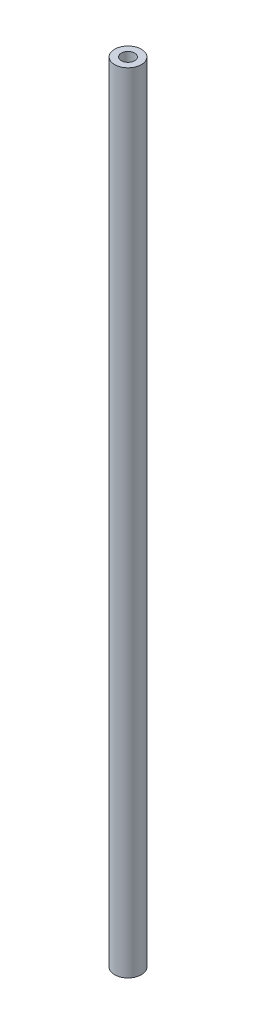
SolidWorks part; units mm, degrees
ref_plane "Front Plane" through (0, 0, 0) normal (0, 0, 1) x (1, 0, 0)
ref_plane "Top Plane" through (0, 0, 0) normal (0, 1, 0) x (1, 0, 0)
ref_plane "Right Plane" through (0, 0, 0) normal (1, 0, 0) x (0, 0, -1)
sketch "Sketch1" plane through (0, 0, 0) normal (0, 1, 0) x (1, 0, 0)
  circle A0 centre (0, 0) radius 6.35
  circle A1 centre (0, 0) radius 3.175
  dimension "D1" = 12.7
  dimension "D2" = 6.35
extrude "Boss-Extrude1" add sketch "Sketch1" along normal blind 374.65
